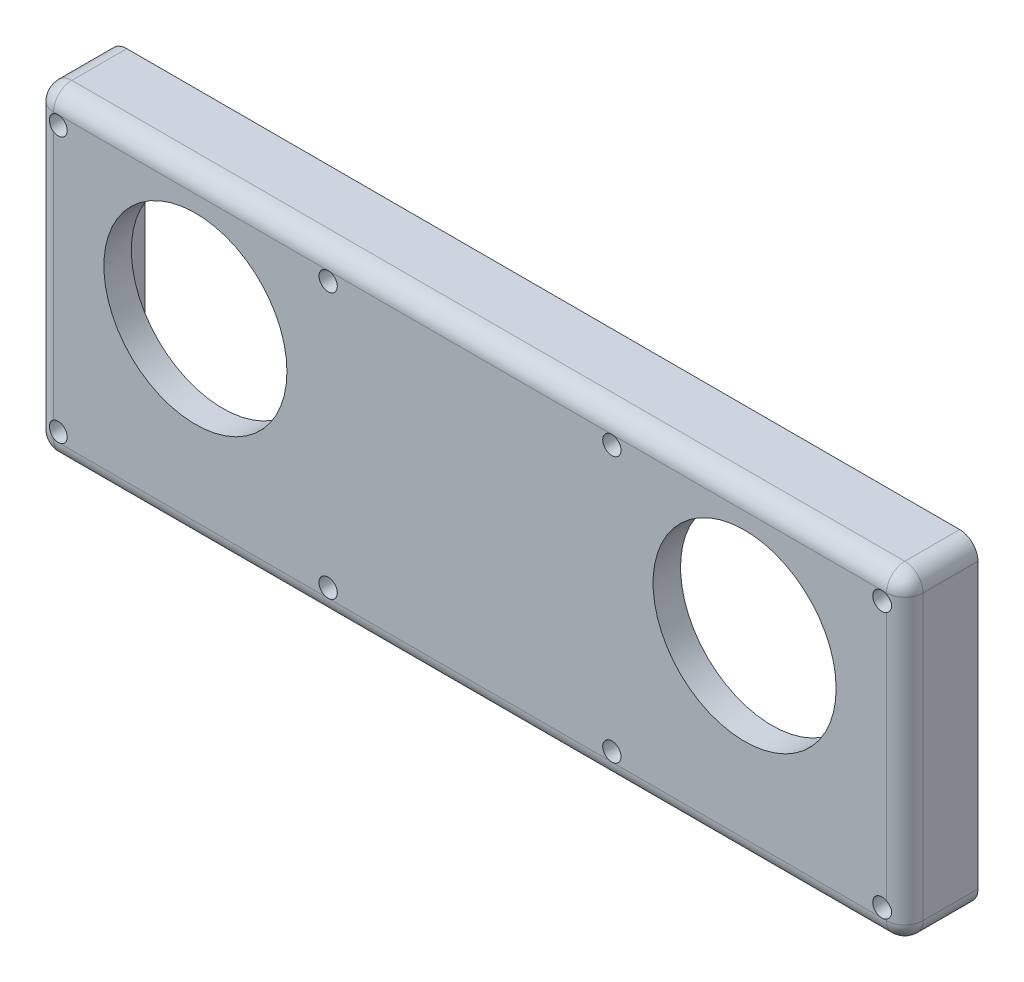
SolidWorks part; units mm, degrees
ref_plane "Front Plane" through (0, 0, 0) normal (0, 0, 1) x (1, 0, 0)
ref_plane "Top Plane" through (0, 0, 0) normal (0, 1, 0) x (1, 0, 0)
ref_plane "Right Plane" through (0, 0, 0) normal (1, 0, 0) x (0, 0, -1)
sketch "Sketch2" plane through (0, 0, 0) normal (0, 0, 1) x (1, 0, 0)
  line L0 (-59.1429, 44.8314) -> (33.8571, 44.8314)
  line L1 (33.8571, 44.8314) -> (33.8571, 12.8314)
  line L2 (33.8571, 12.8314) -> (-59.1429, 12.8314)
  line L3 (-59.1429, 12.8314) -> (-59.1429, 44.8314)
  circle A0 centre (-57.6429, 43.3314) radius 1
  circle A1 centre (-57.6429, 14.3314) radius 1
  circle A2 centre (-28.1429, 43.3314) radius 1
  circle A3 centre (2.8571, 43.3314) radius 1
  circle A4 centre (2.8571, 14.3314) radius 1
  circle A5 centre (-28.1429, 14.3314) radius 1
  circle A6 centre (32.3571, 14.3314) radius 1
  circle A7 centre (32.3571, 43.3314) radius 1
extrude "Boss-Extrude1" add sketch "Sketch2" along normal blind 3
sketch "Sketch6" plane through (0, 0, 3) normal (0, 0, 1) x (1, 0, 0)
  line L0 (-12.6429, 44.8314) -> (33.8571, 28.8314)
  line L1 (33.8571, 44.8314) -> (-59.1429, 44.8314) construction
  line L2 (33.8571, 12.8314) -> (33.8571, 44.8314) construction
  line L3 (33.8571, 28.8314) -> (-12.6429, 29.5401)
  line L5 (-60.1429, 12.0401) -> (34.8571, 12.0401)
  line L6 (-60.1429, 12.0401) -> (-60.1429, 47.0401)
  line L7 (-60.1429, 47.0401) -> (34.8571, 47.0401)
  line L8 (34.8571, 12.0401) -> (34.8571, 47.0401)
  line L9 (-60.1429, 12.0401) -> (34.8571, 47.0401) construction
  line L10 (-60.1429, 47.0401) -> (34.8571, 12.0401) construction
  line M1 (-59.1429, 44.8314) -> (-59.1429, 12.8314)
  line M2 (-59.1429, 12.8314) -> (33.8571, 12.8314)
  line M3 (33.8571, 12.8314) -> (33.8571, 44.8314)
  line M4 (33.8571, 44.8314) -> (-59.1429, 44.8314)
extrude "Boss-Extrude2" add sketch "Sketch6" against normal up to surface (3 mm away) contours L5 L8 L7 L6 M1 M4 M3 M2 region at (-60.0417, 29.5401, 3) up to face at (33.3571, 14.3314, 0)
sketch "Sketch8" plane through (0, 0, 0) normal (0, 0, -1) x (-1, 0, 0)
  line L0 (-34.8571, 47.0401) -> (-34.8571, 46.3314)
  line L1 (-34.8571, 12.0401) -> (-34.8571, 47.0401) construction
  line L2 (-32.8571, 46.3314) -> (58.1429, 46.3314) construction
  line L3 (-34.8571, 46.3314) -> (60.1429, 46.3314)
  line L4 (60.1429, 12.0401) -> (60.1429, 47.0401) construction
  line L5 (60.1429, 46.3314) -> (60.1429, 47.0401)
  line L6 (60.1429, 47.0401) -> (-34.8571, 47.0401)
extrude "Cut-Extrude6" cut sketch "Sketch8" against normal blind 10
sketch "Sketch9" plane through (0, 0, 3) normal (0, 0, 1) x (1, 0, 0)
  line L0 (34.8571, 12.0401) -> (34.8571, 11.3301)
  line L1 (-60.1429, 12.0401) -> (34.8571, 12.0401)
  line L2 (34.8571, 11.3301) -> (-60.1429, 11.3301)
  line L3 (-60.1429, 11.3301) -> (-60.1429, 12.0401)
extrude "Boss-Extrude3" add sketch "Sketch9" against normal up to surface (3 mm away) up to face at (-12.6429, 29.1858, 0)
sketch "Sketch10" plane through (0, 0, 3) normal (0, 0, 1) x (1, 0, 0)
  line L0 (-12.6429, 46.3314) -> (-42.6429, 32.5314)
  line L1 (34.8571, 46.3314) -> (-60.1429, 46.3314) construction
  line L2 (-42.6429, 32.5314) -> (-42.6429, 46.3314)
  line L3 (-42.6429, 46.3314) -> (17.3571, 46.3314)
  line L4 (17.3571, 46.3314) -> (17.3571, 32.5314)
  circle A0 centre (-42.6429, 32.5314) radius 10
  circle A1 centre (17.3571, 32.5314) radius 10
extrude "Cut-Extrude7" cut sketch "Sketch10" against normal blind 10 contours L2 A0 L0 | L0 A0 L2 | A1 region at (24.2282, 39.4025, 3) region at (-43.3974, 31.3539, 3) region at (-39.2378, 37.8458, 3)
sketch "Sketch11" plane through (0, 0, 0) normal (0, 0, -1) x (-1, 0, 0)
  line L0 (60.1429, 11.3301) -> (-34.8571, 11.3301) construction
  line L1 (-34.8571, 46.3314) -> (60.1429, 46.3314)
  line L2 (-34.8571, 46.3314) -> (-34.8571, 11.3301)
  line L3 (-34.8571, 11.3301) -> (60.1429, 11.3301)
  line L4 (60.1429, 46.3314) -> (60.1429, 11.3301)
  line L5 (-34.8571, 46.3314) -> (60.1429, 11.3301)
  line L7 (-30.8571, 15.8308) -> (56.1429, 15.8308)
  line L8 (-30.8571, 15.8308) -> (-30.8571, 41.8308)
  line L9 (-30.8571, 41.8308) -> (56.1429, 41.8308)
  line L10 (56.1429, 15.8308) -> (56.1429, 41.8308)
  line L11 (-30.8571, 15.8308) -> (56.1429, 41.8308) construction
  line L12 (-30.8571, 41.8308) -> (56.1429, 15.8308) construction
  point P7 (12.6429, 28.8308)
  circle M1 centre (42.6429, 32.5314) radius 10
  circle M2 centre (-17.3571, 32.5314) radius 10
  line M3 (60.1429, 46.3314) -> (-34.8571, 46.3314)
  line M4 (-34.8571, 46.3314) -> (-34.8571, 11.3301)
  line M5 (-34.8571, 11.3301) -> (60.1429, 11.3301)
  line M6 (60.1429, 11.3301) -> (60.1429, 46.3314)
  circle M7 centre (-32.3571, 14.3314) radius 1
  circle M8 centre (-2.8571, 14.3314) radius 1
  circle M9 centre (28.1429, 43.3314) radius 1
  circle M10 centre (57.6429, 43.3314) radius 1
  circle M11 centre (57.6429, 14.3314) radius 1
  circle M12 centre (-2.8571, 43.3314) radius 1
  circle M13 centre (28.1429, 14.3314) radius 1
  circle M14 centre (-32.3571, 43.3314) radius 1
extrude "Boss-Extrude7" add sketch "Sketch11" along normal blind 5 contours L10 L7 L5 L9 M6 M3 M2 M1 M10 M12 M11 M9 | L8 L9 L5 L7 M4 M5 M7 M13 M14 M8 region at (29.0993, 43.1311, 0) region at (-12.6429, 45.319, 0)
fillet "Fillet1" radius 2 6 edges at (-12.6429, 11.3301, 3) (-12.6429, 46.3314, 3) (34.8571, 11.3301, -1) (34.8571, 46.3314, -1) (-60.1429, 46.3314, -1) (-60.1429, 11.3301, -1)
fillet "Fillet2" radius 2 6 edges at (34.2713, 11.9159, 2.4142) (34.2713, 45.7456, 2.4142) (-59.5571, 11.9159, 2.4142) (-59.5571, 45.7456, 2.4142) (34.8571, 28.8308, 3) (-60.1429, 28.8308, 3)
